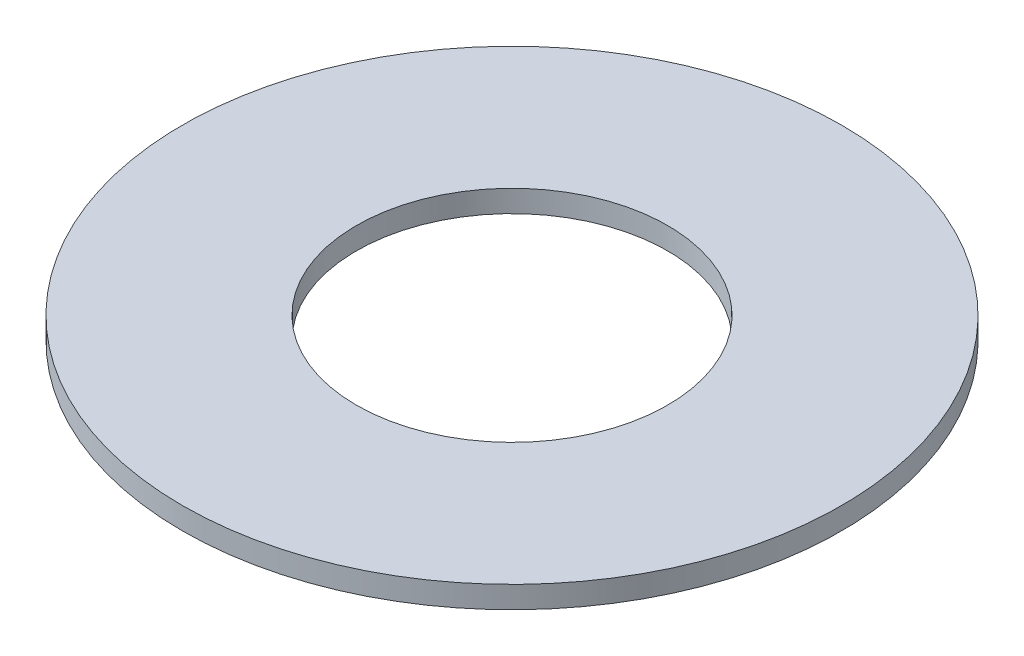
SolidWorks part; units mm, degrees
ref_plane "Front Plane" through (0, 0, 0) normal (0, 0, 1) x (1, 0, 0)
ref_plane "Top Plane" through (0, 0, 0) normal (0, 1, 0) x (1, 0, 0)
ref_plane "Right Plane" through (0, 0, 0) normal (1, 0, 0) x (0, 0, -1)
sketch "Sketch1" plane through (0, 0, 0) normal (0, 1, 0) x (1, 0, 0)
  circle A0 centre (0, 0) radius 90
  dimension "FLANGE_OD" = 180
extrude "Boss-Extrude1" add sketch "Sketch1" along normal blind 6
sketch "Sketch2" plane through (0, 0, 0) normal (0, 1, 0) x (1, 0, 0)
  circle A0 centre (0, 0) radius 42.5
  dimension "BORE_D" = 85
extrude "Cut-Extrude1" cut sketch "Sketch2" along normal through all
sketch "Sketch3" plane through (0, 6, 0) normal (0, 1, 0) x (1, 0, 0)
  circle A0 centre (0, 0) radius 27.8998 construction
  circle A1 centre (-27.8998, 0) radius 2.1425
  dimension "BOLT_D" = 4.285
  dimension "BOLT_PCD" = 55.7995
extrude "Cut-Extrude2" cut sketch "Sketch3" against normal blind 5.9454 rebuild error yes
pattern_circular "CirPattern1" count 8 over 360 rebuild error yes
